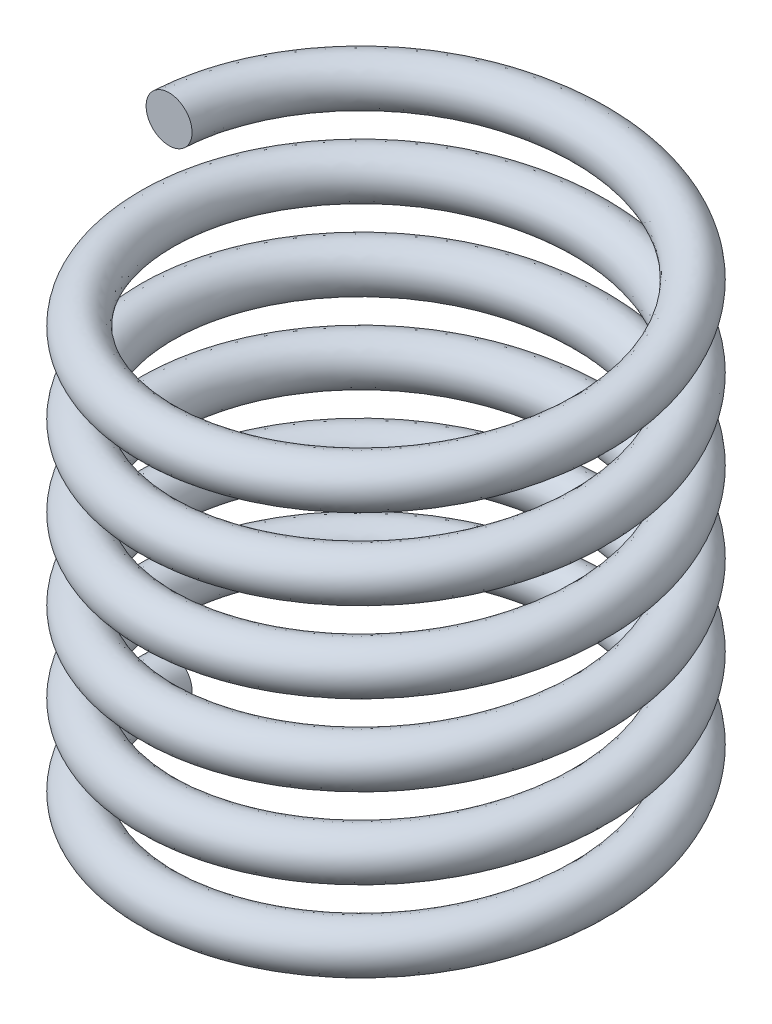
SolidWorks part; units mm, degrees
note: '?' marks a value the reader was unsure of.
material "Chrome Stainless Steel"
ref_plane "Front Plane" through (0, 0, 0) normal (0, 0, 1) x (1, 0, 0)
ref_plane "Top Plane" through (0, 0, 0) normal (0, 1, 0) x (1, 0, 0)
ref_plane "Right Plane" through (0, 0, 0) normal (1, 0, 0) x (0, 0, -1)
ref_axis "X-axis" through (-88.99, 0, 0) along (1, 0, 0)?
ref_axis "Y-axis" through (0, -55, 0) along (0, 1, 0)?
ref_axis "Z-axis" through (0, 0, 55) along (0, 0, -1)?
sketch "Sketch1" plane through (0, 0, 0) normal (0, 1, 0) x (1, 0, 0)
  circle A0 centre (0, 0) radius 2.9972
  dimension "D1" = 5.9944
curve "Helix/Spiral1" pitch 1.1134 height 6.6802 turns 6
sketch "Sketch2" plane through (0, 0, 0) normal (0, 0, 1) x (1, 0, 0)
  circle A0 centre (-2.9972, 0) radius 0.3175
  dimension "D1" = 0.635
sweep "Sweep1" add profiles "Sketch2" path "Helix/Spiral1"
